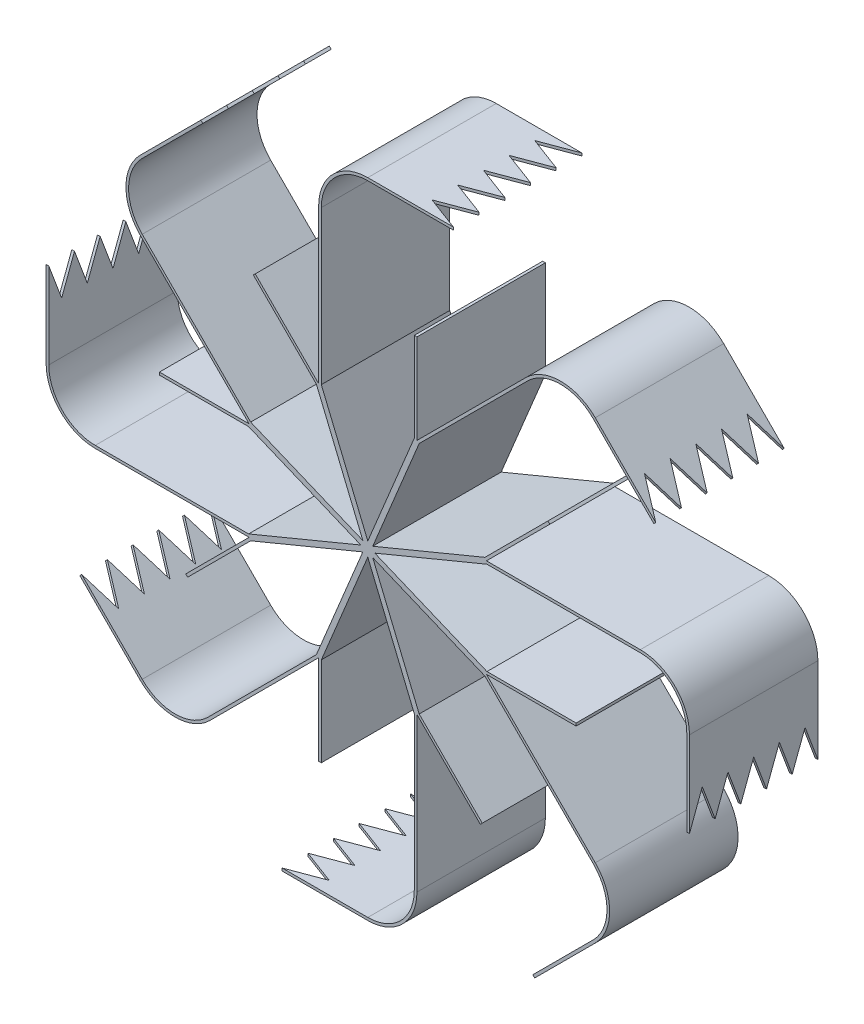
SolidWorks part; units mm, degrees
ref_plane "Front Plane" through (0, 0, 0) normal (0, 0, 1) x (1, 0, 0)
ref_plane "Top Plane" through (0, 0, 0) normal (0, 1, 0) x (1, 0, 0)
ref_plane "Right Plane" through (0, 0, 0) normal (1, 0, 0) x (0, 0, -1)
sketch "Sketch2" plane through (0, 0, 0) normal (0, 0, 1) x (1, 0, 0)
  line L0 (0, 0) -> (0, -127) construction
  line L1 (0, 0) -> (29.1605, -70.3996)
  line L2 (0, 0) -> (-29.1605, -70.3996)
  line L3 (-29.1605, -70.3996) -> (-29.1605, -123.6069)
  line L5 (0, 0) -> (0, -127) construction
  line L6 (29.1605, -123.6069) -> (29.1605, -70.3996)
  line L7 (29.1605, -123.6069) -> (29.1605, -161.7069)
  line L8 (-50.8, -190.8674) -> (0, -190.8674)
  line L9 (-50.8, -189.2799) -> (0, -189.2799)
  line L10 (27.573, -123.6069) -> (27.573, -161.7069)
  line L11 (27.573, -123.6069) -> (27.573, -70.7154)
  line L12 (0, -4.1483) -> (27.573, -70.7154)
  line L13 (0, -4.1483) -> (-27.573, -70.7154)
  line L14 (-27.573, -70.7154) -> (-27.573, -123.6069)
  line L15 (-27.573, -123.6069) -> (-29.1605, -123.6069)
  line L16 (-50.8, -189.2799) -> (-50.8, -190.8674)
  circle A0 centre (0, 0) radius 127 construction
  circle A1 centre (0, 0) radius 76.2 construction
  arc A2 (29.1605, -161.7069) -> (0, -190.8674) centre (0, -161.7069) cw
  arc A3 (27.573, -161.7069) -> (0, -189.2799) centre (0, -161.7069) cw
  dimension "D2" = 152.4
  dimension "D6" = 1.5875
  dimension "D1" = 127
  dimension "D3" = 38.1
  dimension "D4" = 50.8
  dimension "D5" = 45
extrude "Boss-Extrude1" add sketch "Sketch2" along normal blind 76.2
ref_axis "Axis1" through (0, 0, -3.81) along (0, 0, 1)
sketch "Sketch5" plane through (0, -190.8674, 0) normal (0, -1, 0) x (1, 0, 0)
  line L0 (-50.8, 76.2) -> (-30.48, 68.58)
  line L1 (-30.48, 68.58) -> (-50.8, 60.96)
  line L2 (-50.8, 76.2) -> (-50.8, 0) construction
  line L3 (-50.8, 60.96) -> (-30.48, 53.34)
  line L4 (-30.48, 53.34) -> (-50.8, 45.72)
  line L5 (-50.8, 45.72) -> (-30.48, 38.1)
  line L6 (-30.48, 38.1) -> (-50.8, 30.48)
  line L7 (-50.8, 30.48) -> (-30.48, 22.86)
  line L8 (-30.48, 22.86) -> (-50.8, 15.24)
  line L9 (-50.8, 15.24) -> (-30.48, 7.62)
  line L10 (-30.48, 7.62) -> (-50.8, 0)
  line L11 (-50.8, 0) -> (-53.34, 0)
  line L12 (-53.34, 0) -> (-53.34, 76.2)
  line L13 (-53.34, 76.2) -> (-50.8, 76.2)
  dimension "D1" = 15.24
  dimension "D2" = 15.24
  dimension "D3" = 15.24
  dimension "D4" = 15.24
  dimension "D5" = 20.32
  dimension ".1" = 2.54
extrude "Cut-Extrude2" cut sketch "Sketch5" against normal up to next (1.5875 mm away)
pattern_circular "CirPattern10" count 8 over 360 about axis through (0, 0, -3.81) along (0, 0, 1) of "Cut-Extrude2", "Boss-Extrude1"
